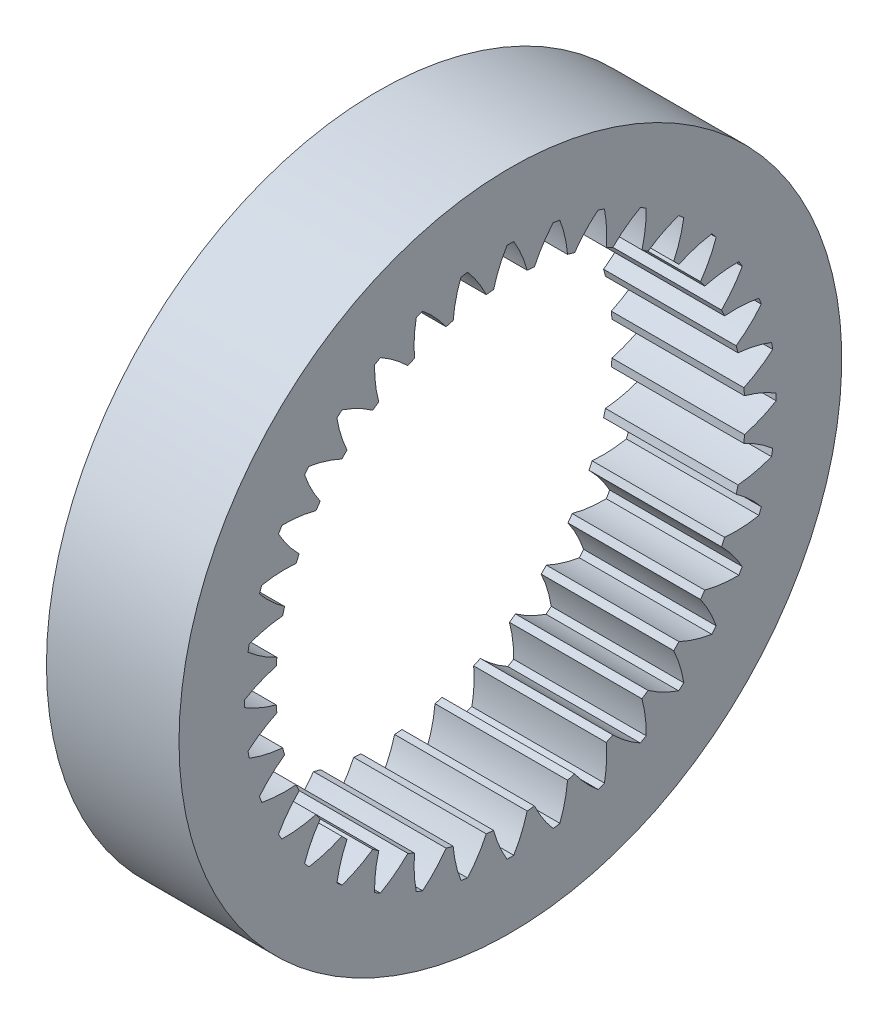
SolidWorks part; units mm, degrees
ref_plane "Plane1" through (0, 0, 0) normal (0, 0, 1) x (1, 0, 0)
ref_plane "Plane2" through (0, 0, 0) normal (0, 1, 0) x (1, 0, 0)
ref_plane "Plane3" through (0, 0, 0) normal (1, 0, 0) x (0, 0, -1)
sketch "HoldingSke" plane through (0, 0, 0) normal (0, 1, 0) x (1, 0, 0)
  line L0 (0, 0) -> (0.6472, -0.4702)
  line L1 (-15, 0) -> (100, 0) construction
  line L2 (0, 0) -> (-2.1039, 2.3779)
  line L3 (0, 0) -> (-11.863, 4.5341)
  line L4 (0, 0) -> (6.9867, 5.0761)
  line L5 (0, 0) -> (-23.7986, -8.8762)
  line L6 (0, 0) -> (-10.5278, -7.1032)
  line L7 (-2.1039, 2.3779) -> (3.3635, 27.1825)
  line L8 (-76.2, 3.6279) -> (-54.61, 3.6279)
  line L9 (-71.009, 38.7566) -> (-53.1078, 45.2721)
  line L10 (-76.2, 71.12) -> (104.1128, 71.12)
  line L11 (0, 0) -> (-12, 0)
  line L12 (-76.2, 101.6) -> (-76.155, 101.6)
  line L13 (24.9733, 27.94) -> (52.9518, 28.4284)
  line L14 (24.9733, 27.94) -> (24.9743, 27.94)
  line L15 (24.9733, 27.94) -> (100.4006, 29.5858)
  circle A0 centre (0, 0) radius 30
  circle A1 centre (0, 0) radius 12.7
  circle A2 centre (0, 0) radius 12.7
  dimension "MHD" = 25.4
  dimension "Hub_dia" = 25.4
  dimension "Diameter" = 60
  dimension "Num_teeth" = 36
  dimension "Pitch_radius" = 180.3128
  dimension "Pitch" = 0.8
  dimension "Width" = 12
  dimension "Overall_len" = 25.4
  dimension "Show_teeth" = 36
  dimension "Thickness" = 12.7
  dimension "OAL" = 25.4001
  dimension "T_dim" = 21.59
  dimension "Ap" = 20
  dimension "H" = 19.05
  dimension "Backlash" = 0.045
  dimension "Addendum_fac" = 1
  dimension "Dedendum_fac" = 1.25
  dimension "Clearance_fac" = 0.25
  dimension "Dedendum_add" = 0.001
  dimension "Module" = 1.25
sketch "BasProSke" plane through (0, 0, 0) normal (0, 1, 0) x (1, 0, 0)
  line L0 (-10, 0) -> (60, 0) construction
  line L1 (0, 21.25) -> (0, 30)
  line L2 (0, 21.25) -> (12, 21.25)
  line L3 (12, 21.25) -> (12, 30)
  line L4 (12, 30) -> (0, 30)
  dimension "Diameter" = 60
  dimension "Thickness" = 12
  dimension "Inside_diameter" = 42.5
revolve "Base-Revolve" add sketch "BasProSke" angle 360 about L0
sketch "TooCutSke" plane through (0, 0, 0) normal (1, 0, 0) x (0, 0, -1)
  line L3 (1.0939, 22.4734) -> (1.0939, 53.6633) construction
  line L4 (0, 0) -> (0, 59.563) construction
  line L5 (0, 0) -> (-5.9551, 68.0675) construction
  line L6 (-9.3468, 18.2837) -> (36.0403, 22.2546) construction
  circle A0 centre (0, 0) radius 22.5 construction
  circle A1 centre (0, 0) radius 24.0635 construction
  circle A2 centre (0, 0) radius 19.0288 construction
  circle A3 centre (0, 0) radius 21.2246 construction
  arc A4 (1.5267, 21.1696) -> (0.3061, 24.0616) centre (-9.3468, 18.2837) ccw
  arc A5 (1.5267, 21.1696) -> (-1.5267, 21.1696) centre (0, 0) ccw
  arc A6 (0.3061, 24.0616) -> (-0.3061, 24.0616) centre (0, 0) ccw
  arc A7 (-0.3061, 24.0616) -> (-1.5267, 21.1696) centre (9.3468, 18.2837) ccw
  dimension "Pitch_dia" = 45
  dimension "Base_dia" = 38.0576
  dimension "Root_dia" = 48.127
  dimension "Overcut_dia" = 42.4492
  dimension "Flank_rad" = 11.25
  dimension "Half_ang" = 5
  dimension "Half_CT" = 1.0939
extrude "ToothCut" cut sketch "TooCutSke" along normal through all
fillet "Breaks" [suppressed] radius 0.125
fillet "RootFillets" [suppressed] radius 0.3135
pattern_circular "TeethCuts" count 36 every 10 about axis through (-10, 0, 0) along (1, 0, 0) of "RootFillets", "Breaks", "ToothCut"
equation "' \"Module@HoldingSke\" = 6.35"
equation "' \"Num_teeth@HoldingSke\" = 24"
equation "' \"Ap@HoldingSke\" =  14.5"
equation "' \"Width@HoldingSke\" = 12"
equation "' \"Diameter@HoldingSke\" = 8 * 25.4"
equation "' \"Show_teeth@HoldingSke\" = 100"
equation "' \"Backlash@HoldingSke\" = 0.009 * 25.4"
equation "' \"Addendum_fac@HoldingSke\" = 1.0"
equation "' \"Dedendum_fac@HoldingSke\" = 1.25"
equation "' \"Dedendum_add@HoldingSke\" = 0.00005 * 25.4"
equation "' \"Clearance_fac@HoldingSke\" = 0.25"
equation "\"Pitch@HoldingSke\" = 1 / \"Module@HoldingSke\" "
equation "\"Overcut_dia@TooCutSke\" = (\"Num_teeth@HoldingSke\" - 2 * \"Addendum_fac@HoldingSke\") / \"Pitch@HoldingSke\" - 0.002 * 25.4"
equation "\"Pitch_dia@TooCutSke\" = \"Num_teeth@HoldingSke\" / \"Pitch@HoldingSke\""
equation "\"Base_dia@TooCutSke\" = \"Num_teeth@HoldingSke\" / \"Pitch@HoldingSke\" * cos((\"Ap@HoldingSke\"  * 3.14159265 / 180)) * 0.90"
equation "\"Root_dia@TooCutSke\" = \"Num_teeth@HoldingSke\"  / \"Pitch@HoldingSke\" + 2 *  \"Dedendum_fac@HoldingSke\"/ \"Pitch@HoldingSke\" + \"Dedendum_add@HoldingSke\" * 2"
equation "\"Half_ang@TooCutSke\" = 180 / \"Num_teeth@HoldingSke\""
equation "\"Half_CT@TooCutSke\" = \"Num_teeth@HoldingSke\" / \"Pitch@HoldingSke\" * sin((3.14159265 / 2 / \"Num_teeth@HoldingSke\")) / 2 + 10 * \"Backlash@HoldingSke\" / 4"
equation "\"Flank_rad@TooCutSke\" = \"Num_teeth@HoldingSke\" / \"Pitch@HoldingSke\" / 4"
equation "\"Radius@RootFillets\"= \"Clearance_fac@HoldingSke\" / \"Pitch@HoldingSke\" + \"Dedendum_add@HoldingSke\""
equation "\"Break_rad@Breaks\" = 0.02 / \"Pitch@HoldingSke\" * 5"
equation "\"Num_teeth@TeethCuts\" = int( \"Show_teeth@HoldingSke\" ) + 1"
equation "\"Num_teeth@TeethCuts\" = ((sgn( \"Num_teeth@TeethCuts\" - \"Num_teeth@HoldingSke\" )-1)*( \"Num_teeth@TeethCuts\" - \"Num_teeth@HoldingSke\" ))/-2+ \"Num_teeth@HoldingSke\""
equation "\"Num_teeth@TeethCuts\" = ((sgn( \"Num_teeth@TeethCuts\" - 2.0)+1)*( \"Num_teeth@TeethCuts\" - 2.0))/2 +2.0"
equation "\"Angle@TeethCuts\" = 360.0 / \"Num_teeth@HoldingSke\""
equation "\"Diameter@BasProSke\" = \"Num_teeth@HoldingSke\"  / \"Pitch@HoldingSke\" + 2 *  \"Dedendum_fac@HoldingSke\"/ \"Pitch@HoldingSke\" + \"Dedendum_add@HoldingSke\" * 2 + 0.002 * 25.4"
equation "\"Diameter@BasProSke\" = ((sgn( \"Diameter@BasProSke\"  - \"Diameter@HoldingSke\" )+1)*( \"Diameter@BasProSke\"  - \"Diameter@HoldingSke\" ))/2 + \"Diameter@HoldingSke\""
equation "\"Inside_diameter@BasProSke\" =  (\"Num_teeth@HoldingSke\" - 2 * \"Addendum_fac@HoldingSke\") / \"Pitch@HoldingSke\" "
equation "\"Thickness@BasProSke\"  = \"Width@HoldingSke\""
